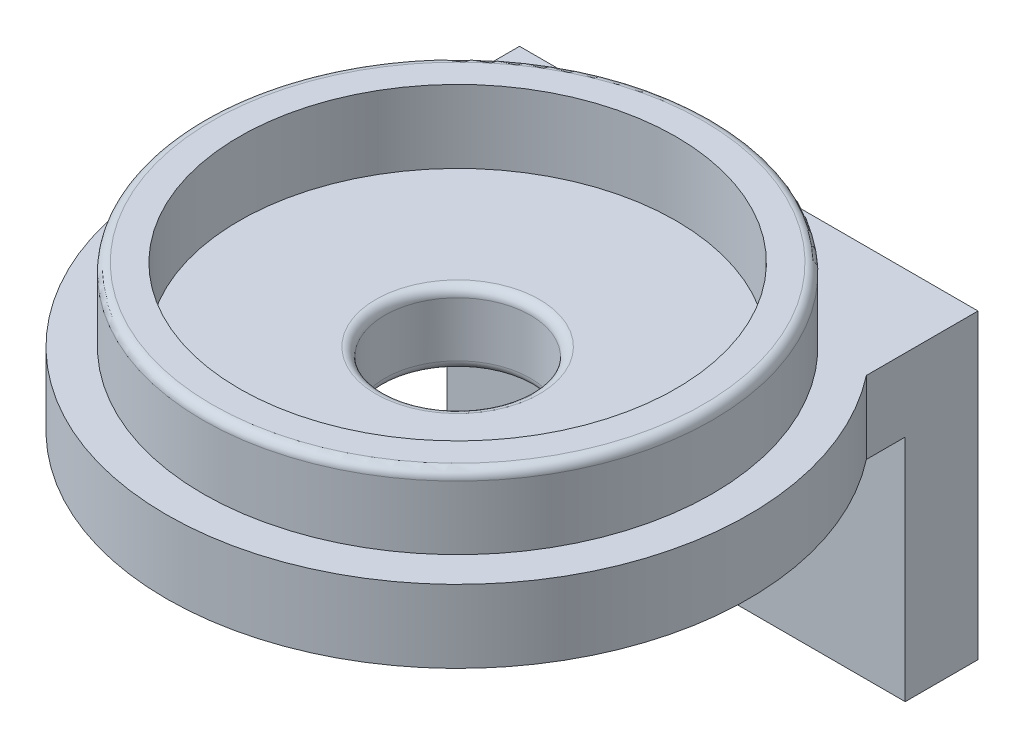
SolidWorks part; units mm, degrees
material "PLA Black"
ref_plane "Front Plane" through (0, 0, 0) normal (0, 0, 1) x (1, 0, 0)
ref_plane "Top Plane" through (0, 0, 0) normal (0, 1, 0) x (1, 0, 0)
ref_plane "Right Plane" through (0, 0, 0) normal (1, 0, 0) x (0, 0, -1)
sketch "Sketch1" plane through (0, 0, 0) normal (1, 0, 0) x (0, 0, -1)
  line L0 (0, -32.3252) -> (0, 32.3252) construction
  line L1 (22.225, 9.525) -> (22.225, 3.175)
  line L2 (22.225, 3.175) -> (25.4, 3.175)
  line L3 (25.4, 3.175) -> (25.4, -3.175)
  line L8 (19.05, 9.525) -> (22.225, 9.525)
  line L13 (19.05, 3.175) -> (19.05, 9.525)
  line L14 (19.05, 3.175) -> (6.35, 3.175)
  line L15 (6.35, 3.175) -> (6.35, -3.175)
  line L16 (6.35, -3.175) -> (25.4, -3.175)
  point P4 (0, 0)
  point P12 (25.4, 0)
  dimension "D1" = 3.175
  dimension "D2" = 6.35
  dimension "D3" = 6.35
  dimension "D4" = 50.8
  dimension "D5" = 12.7
revolve "Revolve1" add sketch "Sketch1" angle 360 about L0
fillet "Fillet1" radius 0.7937 3 edges at (0, 9.525, -22.225) (0, -3.175, -6.35) (0, 3.175, -6.35)
sketch "Sketch2" plane through (0, 0, 0) normal (1, 0, 0) x (0, 0, -1)
  line L0 (-25.4, -3.175) -> (25.4, -3.175) construction
  line L1 (25.4, 3.175) -> (12.7, 3.175)
  line L2 (25.4, 3.175) -> (25.4, -3.175)
  line L3 (19.05, -3.175) -> (12.7, -3.175)
  line L4 (12.7, 3.175) -> (12.7, -3.175)
  line L5 (25.4, 3.175) -> (12.7, -3.175) construction
  line L6 (25.4, -3.175) -> (12.7, 3.175) construction
  line L9 (25.4, -3.175) -> (25.4, -23.175)
  line L10 (25.4, -23.175) -> (19.05, -23.175)
  line L11 (19.05, -3.175) -> (19.05, -23.175)
  line L12 (25.4, -3.175) -> (19.05, -23.175) construction
  line L13 (25.4, -23.175) -> (19.05, -3.175) construction
  point P4 (19.05, 0)
  point P11 (22.225, -13.175)
  point P12 (25.4, -4.0813)
  dimension "D1" = 12.7
  dimension "D2" = 20
  dimension "D3" = 6.35
extrude "Boss-Extrude1" add sketch "Sketch2" along normal mid plane 40
sketch "Sketch3" plane through (0, 0, -19.05) normal (0, 0, 1) x (1, 0, 0)
  arc A0 (-10, -15.275) -> (-10, -11.075) centre (-10, -13.175) ccw construction
  arc A1 (10, -15.275) -> (10, -11.075) centre (10, -13.175) ccw construction
  arc A2 (-10, -15.275) -> (-10, -11.075) centre (-10, -13.175) ccw
  arc A3 (10, -15.275) -> (10, -11.075) centre (10, -13.175) ccw
  circle A4 centre (-10, -13.175) radius 2.1
  circle A5 centre (10, -13.175) radius 2.1
extrude "Cut-Extrude1" cut sketch "Sketch3" against normal through all contours A2 A4 | A3 A5 region at (-10, -13.175, -19.05) region at (10, -13.175, -19.05)
